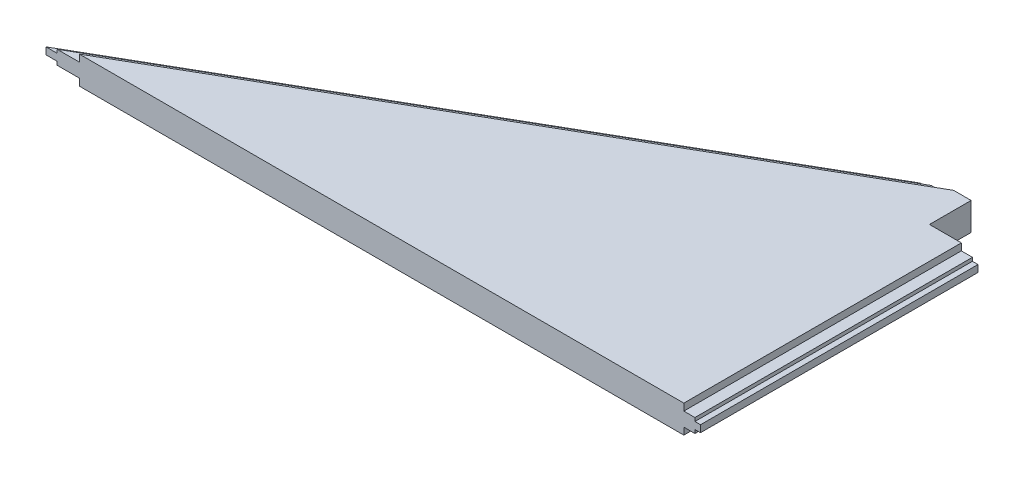
SolidWorks part; units mm, degrees
material "Dragonplate CF"
ref_plane "Front Plane" through (0, 0, 0) normal (0, 0, 1) x (1, 0, 0)
ref_plane "Top Plane" through (0, 0, 0) normal (0, 1, 0) x (1, 0, 0)
ref_plane "Right Plane" through (0, 0, 0) normal (1, 0, 0) x (0, 0, -1)
sketch "Sketch1" plane through (0, 0, 0) normal (0, 1, 0) x (1, 0, 0)
  line L0 (-406.4, 0) -> (0, 0)
  line L1 (0, 0) -> (0, 146.05)
  line L2 (0, 146.05) -> (-152.4, 146.05)
  line L3 (-152.4, 146.05) -> (-406.4, 0)
  dimension "D1" = 406.4
  dimension "D2" = 152.4
  dimension "D3" = 146.05
extrude "Boss-Extrude1" add sketch "Sketch1" along normal blind 6.35 and the other way blind 6.35 contours L3 L0 L1 L2
sketch "Sketch2" plane through (-100.9796, 0, -175.6167) normal (-0.4985, 0, -0.8669) x (-0.8669, 0, 0.4985)
  line L0 (59.3148, 6.35) -> (59.3148, 3.175)
  line L1 (59.3148, -6.35) -> (59.3148, 6.35) construction
  line L2 (59.3148, 3.175) -> (352.3107, 3.175)
  line L3 (352.3107, -6.35) -> (352.3107, 6.35) construction
  line L4 (352.3107, 3.175) -> (352.3107, 6.35)
  line L5 (352.3107, 6.35) -> (59.3148, 6.35)
  line L6 (59.3148, -6.35) -> (59.3148, -3.175)
  line L7 (59.3148, -6.35) -> (352.3107, -6.35)
  line L8 (352.3107, -6.35) -> (352.3107, -3.175)
  line L9 (352.3107, -3.175) -> (59.3148, -3.175)
  dimension "D1" = 3.175
  dimension "D2" = 3.175
extrude "Cut-Extrude1" cut sketch "Sketch2" against normal blind 38.1
sketch "Sketch3" plane through (0, 0, 0) normal (1, 0, 0) x (0, 0, -1)
  line L0 (0, 6.35) -> (0, 3.175)
  line L2 (0, 6.35) -> (146.05, 6.35)
  line L3 (146.05, 6.35) -> (146.05, 3.175)
  line L4 (146.05, -6.35) -> (146.05, 6.35) construction
  line L5 (0, 3.175) -> (146.05, 3.175)
  line L6 (0, -6.35) -> (0, -3.175)
  line L7 (0, -3.175) -> (146.05, -3.175)
  line L8 (146.05, -3.175) -> (146.05, -6.35)
  line L9 (146.05, -6.35) -> (0, -6.35)
  dimension "D1" = 3.175
  dimension "D2" = 3.175
  dimension "D3" = 3.175
  dimension "D4" = 3.175
extrude "Cut-Extrude2" cut sketch "Sketch3" against normal blind 38.1
sketch "Sketch4" plane through (0, 6.35, 0) normal (0, 1, 0) x (1, 0, 0)
  line L0 (-133.4083, 113.0209) -> (-75.9663, 146.05)
  line L1 (-38.1, 146.05) -> (-152.4, 146.05) construction
  line L2 (-75.9663, 146.05) -> (-152.4, 146.05)
  line L3 (-152.4, 146.05) -> (-133.4083, 113.0209)
  line L4 (-329.9663, 0) -> (-133.4083, 113.0209) construction
extrude "Cut-Extrude3" cut sketch "Sketch4" against normal blind 3.175
sketch "Sketch5" plane through (0, -6.35, 0) normal (0, -1, 0) x (1, 0, 0)
  line L0 (-133.4083, -113.0209) -> (-75.9663, -146.05)
  line L1 (-38.1, -146.05) -> (-152.4, -146.05) construction
  line L2 (-75.9663, -146.05) -> (-152.4, -146.05)
  line L3 (-152.4, -146.05) -> (-133.4083, -113.0209)
  line L4 (-329.9663, 0) -> (-133.4083, -113.0209) construction
extrude "Cut-Extrude4" cut sketch "Sketch5" against normal blind 3.175
sketch "Sketch6" plane through (0, 0, -146.05) normal (0, 0, -1) x (-1, 0, 0)
  line L0 (38.1, 6.35) -> (0, 0) construction
  line L1 (0, 0) -> (38.1, -6.35) construction
  line L2 (0, -3.175) -> (0, 3.175) construction
  line L3 (38.622, 3.2182) -> (19.3128, 0) construction
  line L4 (19.3128, 0) -> (38.622, -3.2182) construction
  line L5 (38.1, -3.175) -> (43.18, -3.175)
  line L6 (43.18, -3.175) -> (43.18, -6.35)
  line L7 (38.1, -6.35) -> (75.9663, -6.35) construction
  line L8 (43.18, -6.35) -> (38.1, -6.35)
  line L9 (38.1, 3.175) -> (43.18, 3.175)
  line L10 (43.18, 3.175) -> (43.18, 6.35)
  line L11 (38.1, 6.35) -> (75.9663, 6.35) construction
  line L12 (43.18, 6.35) -> (38.1, 6.35)
  line L13 (38.1, 6.35) -> (0, 6.35)
  line L14 (0, 6.35) -> (0, -6.35)
  line L15 (0, -6.35) -> (38.1, -6.35)
  line L16 (38.1, -3.175) -> (38.1, -1.5875)
  line L22 (38.1, -1.5875) -> (35.56, -1.5875)
  line L23 (35.56, -1.5875) -> (35.56, 1.5875)
  line L24 (35.56, 1.5875) -> (38.1, 1.5875)
  line L25 (38.1, 1.5875) -> (38.1, 3.175)
  line M7 (75.9663, 6.35) -> (38.1, 6.35)
  line M8 (38.1, 6.35) -> (38.1, 3.175)
  line M9 (38.1, 3.175) -> (0, 3.175)
  line M10 (0, 3.175) -> (0, -3.175)
  line M11 (0, -3.175) -> (38.1, -3.175)
  line M12 (38.1, -3.175) -> (38.1, -6.35)
  line M13 (38.1, -6.35) -> (75.9663, -6.35)
  dimension "D2" = 1.5875
  dimension "D1" = 3.175
  dimension "D3" = 5.08
  dimension "D4" = 5.08
  dimension "D5" = 2.54
  dimension "D6" = 3.175
extrude "Cut-Extrude5" cut sketch "Sketch6" against normal blind 157.099 contours L9 L10 M7 M8 | L6 L5 M12 M13 | L4 L3 M11 M9 M10 | L4 L3 region at (-18.4369, 0, -146.05) region at (-40.64, -4.7625, -146.05) region at (-40.64, 4.7625, -146.05)
sketch "Sketch7" plane through (0, -3.175, 0) normal (0, -1, 0) x (1, 0, 0)
  line L0 (-152.4, -146.05) -> (-133.4083, -113.0209) construction
  line L1 (-329.9663, 0) -> (-75.9663, -146.05) construction
  line L2 (-75.9663, -146.05) -> (-329.9663, 0) construction
ref_plane "Plane1" through (-51.4204, 0, 29.5667) normal (-0.8669, 0, 0.4985) x (0.4985, 0, 0.8669)
sketch "Sketch8" plane through (-51.4204, 0, 29.5667) normal (-0.8669, 0, 0.4985) x (0.4985, 0, 0.8669)
  line L0 (-202.5787, 0) -> (-164.4787, 0) construction
  line L1 (-202.5787, -3.175) -> (-202.5787, 3.175) construction
  line L2 (-164.4787, 0) -> (-164.4787, -6.35) construction
  line L3 (-164.4787, -6.35) -> (-202.5787, 0) construction
  line L4 (-202.5787, 0) -> (-164.4787, 6.35) construction
  line L5 (-164.4787, 0) -> (-164.4787, 6.35) construction
  line L6 (-163.9567, -3.2182) -> (-183.2659, 0) construction
  line L7 (-183.2659, 0) -> (-163.9567, 3.2182) construction
  line L8 (-164.4787, 3.175) -> (-159.3987, 3.175)
  line L9 (-159.3987, 3.175) -> (-159.3987, 6.35)
  line L10 (-159.3987, 6.35) -> (-164.4787, 6.35)
  line L11 (-164.4787, -3.175) -> (-159.3987, -3.175)
  line L12 (-159.3987, -3.175) -> (-159.3987, -6.35)
  line L13 (-159.3987, -6.35) -> (-164.4787, -6.35)
  line L14 (-164.4787, 6.35) -> (-202.5787, 6.35)
  line L15 (-202.5787, 6.35) -> (-202.5787, -6.35)
  line L16 (-202.5787, -6.35) -> (-164.4787, -6.35)
  line L17 (-164.4787, -3.175) -> (-164.4787, -1.5875)
  line L23 (-164.4787, -1.5875) -> (-167.0187, -1.5875)
  line L24 (-167.0187, -1.5875) -> (-167.0187, 1.5875)
  line L25 (-167.0187, 1.5875) -> (-164.4787, 1.5875)
  line L26 (-164.4787, 1.5875) -> (-164.4787, 3.175)
  point P7 (-164.4787, -3.175)
  point P11 (-164.4787, 3.175)
  dimension "D5" = 1.5875
  dimension "D1" = 38.1
  dimension "D2" = 6.35
  dimension "D3" = 6.35
  dimension "D6" = 5.08
  dimension "D7" = 3.175
  dimension "D8" = 5.08
  dimension "D9" = 3.175
  dimension "D10" = 38.1
  dimension "D11" = 12.7
  dimension "D12" = 2.54
  dimension "D13" = 3.175
  dimension "D4" = 3.175
extrude "Cut-Extrude6" cut sketch "Sketch8" against normal blind 157.099 and the other way blind 339.217 contours L8 L9 L10 L14 L15 L16 L13 L12 L11 L6 L7 | L7 L6 region at (-142.3615, 0, -128.5917)
sketch "Sketch9" plane through (0, 6.35, 0) normal (0, 1, 0) x (1, 0, 0)
  line L5 (0, 146.05) -> (-50.8, 146.05)
  line L6 (0, 146.05) -> (-152.4, 146.05) construction
  line L7 (-50.8, 146.05) -> (-50.8, 127)
  line L8 (-50.8, 127) -> (0, 127)
  line L9 (0, 0) -> (0, 146.05) construction
  line L10 (0, 146.05) -> (0, 127)
  dimension "D1" = 50.8
  dimension "D2" = 19.05
extrude "Cut-Extrude7" cut sketch "Sketch9" against normal blind 21.59
sketch "Sketch10" plane through (0, 6.35, 0) normal (0, 1, 0) x (1, 0, 0)
  line L0 (-44.68, 127) -> (-44.68, 0) construction
  line L1 (-50.8, 127) -> (-43.18, 127) construction
  line L2 (-319.7751, 0) -> (-43.18, 0) construction
  line L4 (-44.68, 127) -> (-51.765, 127)
  line L5 (-44.68, 127) -> (-44.68, 90.23)
  line L6 (-44.68, 90.23) -> (-51.765, 90.23)
  line L7 (-51.765, 127) -> (-51.765, 90.23)
  line L8 (-51.765, 127) -> (-77.95, 127)
  line L10 (-51.765, 90.23) -> (-77.95, 90.23)
  line L11 (-77.95, 127) -> (-77.95, 90.23)
  line M10 (-43.18, 127) -> (-50.8, 127)
  dimension "D1" = 1.5
  dimension "D2" = 36.77
  dimension "D3" = 7.085
  dimension "D4" = 26.185
extrude "Cut-Extrude9" [suppressed] cut sketch "Sketch10" against normal blind 12.35 contours L8 L11 L10 L7 | L4 L7 L6 L5 M10
sketch "Sketch11" plane through (0, 6.35, 0) normal (0, 1, 0) x (1, 0, 0)
  line L1 (-44.68, 127) -> (-51.765, 127)
  line L2 (-44.68, 127) -> (-44.68, 149.6338)
  line L3 (-44.68, 149.6338) -> (-51.765, 149.6338)
  line L4 (-51.765, 127) -> (-51.765, 149.6338)
  line L5 (-51.765, 127) -> (-57.765, 127)
  line L6 (-51.765, 127) -> (-51.765, 149.6338)
  line L7 (-51.765, 149.6338) -> (-57.765, 149.6338)
  line L8 (-57.765, 127) -> (-57.765, 149.6338)
  line M11 (-50.8, 127) -> (-50.8, 146.05)
  line M12 (-50.8, 146.05) -> (-65.7751, 146.05)
  dimension "D1" = 7.085
  dimension "D2" = 6
extrude "Cut-Extrude10" cut sketch "Sketch11" against normal through all contours L8 L4 M12 | L4 M11 M12 region at (-51.2825, 6.35, -136.525) region at (-54.765, 6.35, -136.525)
sketch "Sketch12" [suppressed] plane through (0, 6.35, 0) normal (0, 1, 0) x (1, 0, 0)
  line L0 (-77.95, 90.23) -> (-103.35, 64.83)
  line L1 (-44.68, 90.23) -> (-77.95, 90.23) construction
  line L2 (-103.35, 64.83) -> (-253.0681, 7.62)
  line L3 (-319.7751, 0) -> (-43.18, 0) construction
  line L4 (-90.65, 77.53) -> (-88.8539, 75.7339) construction
  line L5 (-90.65, 77.53) -> (-92.4461, 79.3261) construction
  line L6 (-147.0885, 48.1167) -> (-146.1819, 45.744) construction
  line L7 (-147.0885, 48.1167) -> (-147.9952, 50.4894) construction
  line L8 (-88.8539, 75.7339) -> (-101.9371, 62.6508)
  line L9 (-88.8539, 75.7339) -> (-74.3579, 90.23)
  line L10 (-92.4461, 79.3261) -> (-77.95, 93.8221)
  line L11 (-77.95, 127) -> (-77.95, 90.23) construction
  line L12 (-92.4461, 79.3261) -> (-104.9589, 66.8132)
  line L13 (-147.9952, 50.4894) -> (-104.9589, 66.8132)
  line L14 (-146.1819, 45.744) -> (-113.5643, 58.2078)
  line L15 (-146.1819, 45.744) -> (-253.0681, 4.9009)
  line L16 (-113.5643, 58.2078) -> (-101.9371, 62.6508)
  line L17 (-147.9952, 50.4894) -> (-253.0681, 10.6349)
  line L18 (-253.0681, 4.9009) -> (-253.0681, 10.6349)
  line L19 (-44.68, 90.23) -> (-77.95, 90.23) construction
  line L20 (-77.95, 93.8221) -> (-77.95, 90.23)
  line L21 (-104.9589, 66.8132) -> (-101.9371, 62.6508) construction
  line M14 (-44.68, 90.23) -> (-77.95, 90.23)
  line M15 (-77.95, 90.23) -> (-77.95, 127)
  dimension "D1" = 135
  dimension "D2" = 25.4
  dimension "D3" = 25.4
  dimension "D4" = 7.62
  dimension "D5" = 90
  dimension "D6" = 90
  dimension "D7" = 2.54
  dimension "D8" = 2.54
  dimension "D9" = 2.54
  dimension "D10" = 2.54
  dimension "D11" = 90
extrude "Cut-Extrude11" [suppressed] cut sketch "Sketch12" against normal blind 5.08 contours L18 L2 L0 L10 L12 L13 L17 M15 | L18 L15 L14 L16 L8 L9 L0 L2 M14
sketch "Sketch15" [suppressed] plane through (0, 6.35, 0) normal (0, 1, 0) x (1, 0, 0)
  line L0 (-77.95, 90.23) -> (-45.45, 90.23) construction
  line L1 (-44.68, 90.23) -> (-74.3579, 90.23) construction
  dimension "D1" = 32.5
